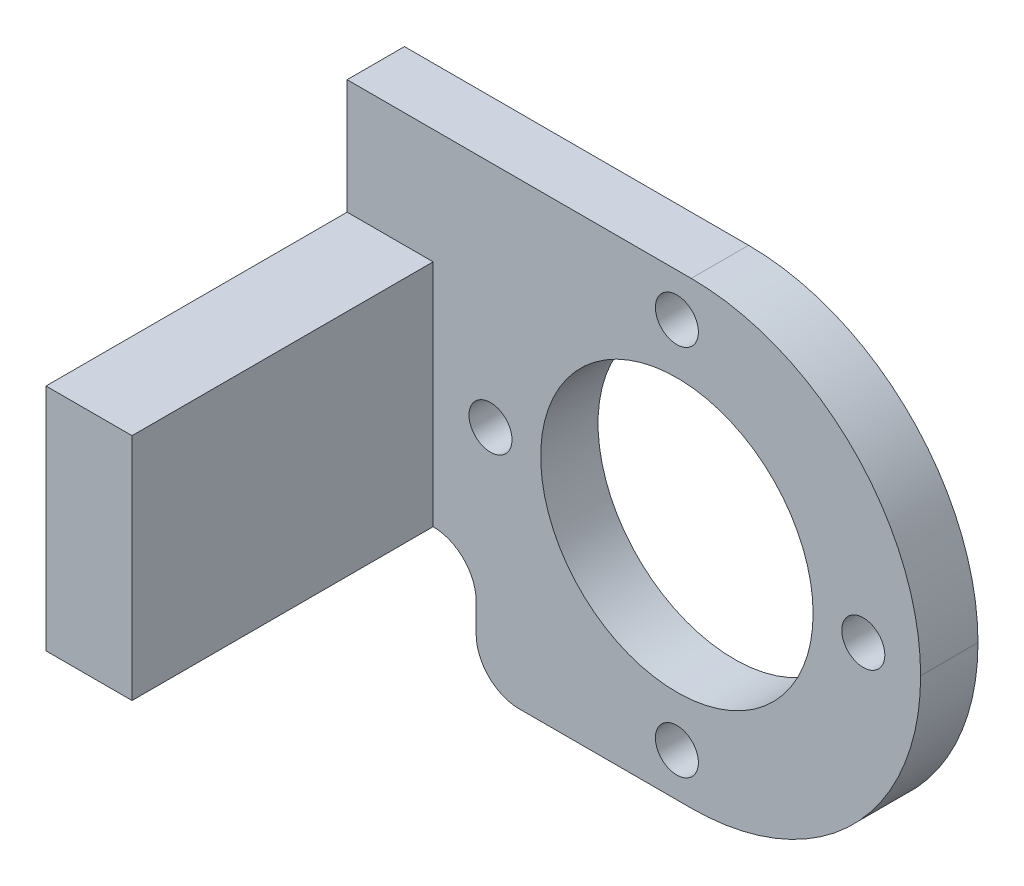
SolidWorks part; units mm, degrees
material "Stainless Steel (ferritic)"
ref_plane "Front Plane" through (0, 0, 0) normal (0, 0, 1) x (1, 0, 0)
ref_plane "Top Plane" through (0, 0, 0) normal (0, 1, 0) x (1, 0, 0)
ref_plane "Right Plane" through (0, 0, 0) normal (1, 0, 0) x (0, 0, -1)
sketch "Sketch1" plane through (0, 0, 0) normal (0, 1, 0) x (1, 0, 0)
  line L0 (-17, 0) -> (17, 0)
  line L1 (17, 0) -> (17, 4)
  line L2 (17, 4) -> (-23, 4)
  line L3 (-23, 4) -> (-23, -21)
  line L4 (-23, -21) -> (-17, -21)
  line L5 (-17, -21) -> (-17, 0)
  dimension "D1" = 34
  dimension "D2" = 6
  dimension "D3" = 4
  dimension "D4" = 25
extrude "Boss-Extrude1" add sketch "Sketch1" along normal mid plane 32
sketch "Sketch2" plane through (-17, 0, 0) normal (1, 0, 0) x (0, 0, -1)
  line L0 (0, 16) -> (0, -16) construction
  line L1 (-21, 16) -> (0, 16)
  line L2 (-21, 16) -> (-21, 8)
  line L3 (-21, 8) -> (0, 8)
  line L4 (0, 16) -> (0, 8)
  line L5 (0, 0) -> (-25.1101, 0) construction
  line L6 (0, -16) -> (0, -8)
  line L7 (-21, -16) -> (0, -16)
  line L8 (-21, -16) -> (-21, -8)
  line L9 (-21, -8) -> (0, -8)
  dimension "D1" = 8
extrude "Cut-Extrude1" cut sketch "Sketch2" against normal through all
sketch "Sketch3" plane through (0, 0, 0) normal (0, 0, 1) x (1, 0, 0)
  circle A0 centre (0, 0) radius 9.5
  dimension "D1" = 19
extrude "Cut-Extrude2" cut sketch "Sketch3" against normal through all
fillet "Fillet1" radius 16 2 edges at (17, -16, -2) (17, 16, -2)
hole_wizard "Ø3.0 (3) Diameter Hole1" positions "Sketch5" profile "Sketch4" hole size "Ø3.0" standard "Ansi Metric" end condition through all
sketch "Sketch5" plane through (0, 0, -4) normal (0, 0, -1) x (-1, 0, 0)
  circle A0 centre (0, 0) radius 13 construction
  point P0 (0, 13)
  point P1 (13, 0)
  point P3 (0, -13)
  point P5 (-13, 0)
  dimension "D1" = 26
sketch "Sketch4" plane through (0, 13, -4) normal (1, 0, 0) x (0, 1, 0)
  line L0 (0, 0) -> (0, 25)
  line L1 (0, 25) -> (1.5, 25)
  line L2 (1.5, 25) -> (1.5, 0)
  line L5 (1.5, 0) -> (0, 0)
  line L11 (0, -6.35) -> (0, 107.95) construction
  dimension "Thru Hole Dia." = 3
  dimension "Thru Hole Depth" = 25
sketch "Sketch6" plane through (0, 0, 0) normal (0, 0, 1) x (1, 0, 0)
  line L0 (-23, -16) -> (1, -16) construction
  line L1 (-23, -8) -> (-14, -8)
  line L2 (-23, -8) -> (-23, -16)
  line L3 (-23, -16) -> (-14, -16)
  line L4 (-14, -8) -> (-14, -16)
  line L5 (-17, 8) -> (-17, -8) construction
  dimension "D1" = 3
extrude "Cut-Extrude3" cut sketch "Sketch6" against normal through all
fillet "Fillet2" radius 3 2 edges at (-14, -16, -2) (-14, -8, -2)
